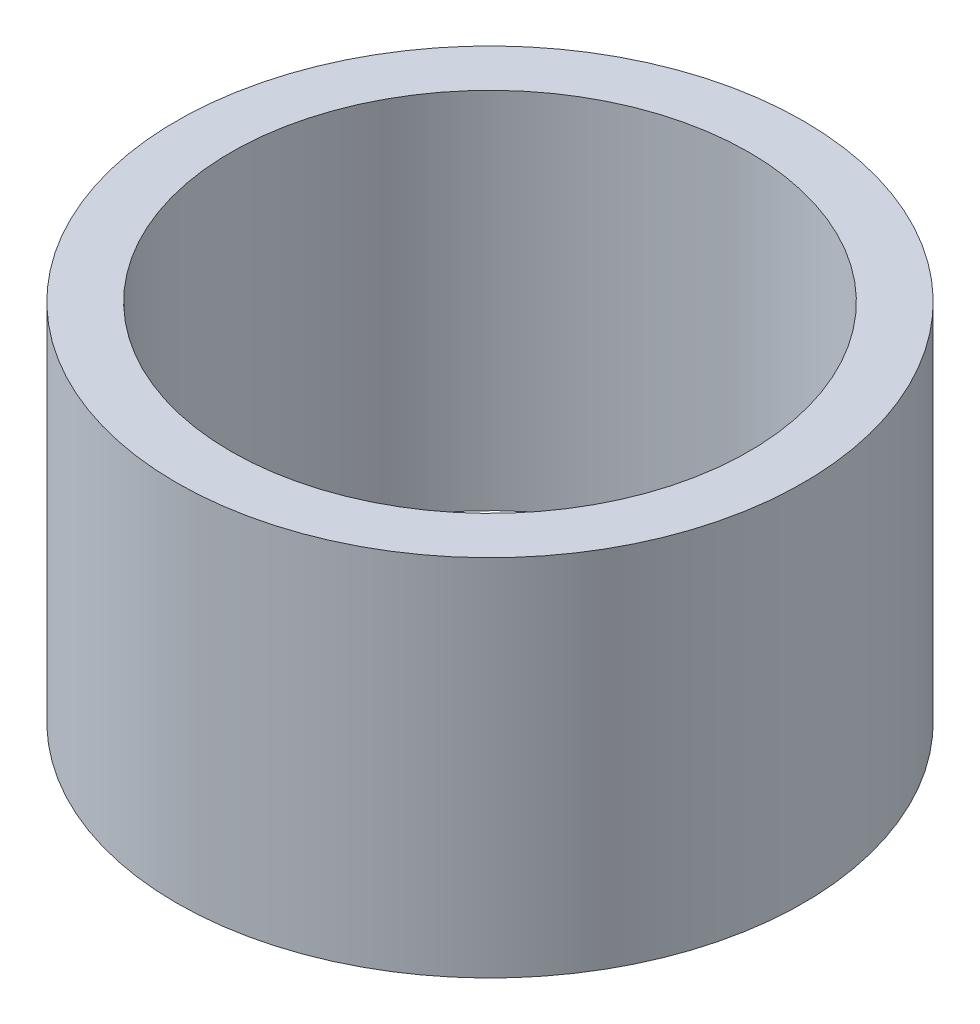
SolidWorks part; units mm, degrees
ref_plane "Front Plane" through (0, 0, 0) normal (0, 0, 1) x (1, 0, 0)
ref_plane "Top Plane" through (0, 0, 0) normal (0, 1, 0) x (1, 0, 0)
ref_plane "Right Plane" through (0, 0, 0) normal (1, 0, 0) x (0, 0, -1)
sketch "Sketch1" plane through (0, 0, 0) normal (0, 1, 0) x (1, 0, 0)
  circle A0 centre (0, 0) radius 27.5
  dimension "SLEEVE_OD" = 55
extrude "Boss-Extrude1" add sketch "Sketch1" along normal blind 31.9412
sketch "Sketch2" plane through (0, 0, 0) normal (0, 1, 0) x (1, 0, 0)
  circle A0 centre (0, 0) radius 22.7332
  dimension "BORE_D" = 45.4663
extrude "Cut-Extrude1" cut sketch "Sketch2" along normal through all
chamfer "Chamfer1" distance 2.4148 angle 45 rebuild error yes
